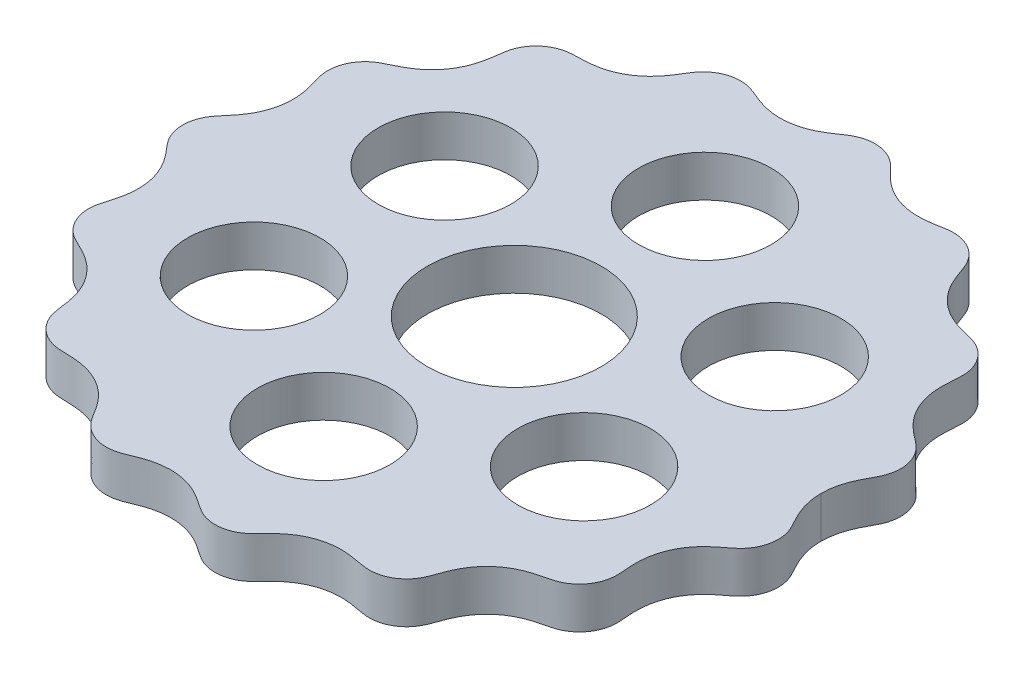
SolidWorks part; units mm, degrees
ref_plane "Front Plane" through (0, 0, 0) normal (0, 0, 1) x (1, 0, 0)
ref_plane "Top Plane" through (0, 0, 0) normal (0, 1, 0) x (1, 0, 0)
ref_plane "Right Plane" through (0, 0, 0) normal (1, 0, 0) x (0, 0, -1)
sketch "Sketch1" plane through (0, 0, 0) normal (0, 1, 0) x (1, 0, 0)
  circle A0 centre (0, 0) radius 10.5
  circle A1 centre (0, 0) radius 23 construction
  circle A2 centre (0, 23) radius 8
  circle A3 centre (19.9186, 11.5) radius 8
  circle A4 centre (19.9186, -11.5) radius 8
  circle A5 centre (0, -23) radius 8
  circle A6 centre (-19.9186, -11.5) radius 8
  circle A7 centre (-19.9186, 11.5) radius 8
  spline S0 degree 4 poles (38.6756, 9.5405) (38.7869, 9.3354) (38.9807, 8.9098) (39.18, 8.2438) (39.2638, 7.3275) (39.17, 6.4698) (38.9321, 5.7015) (38.5995, 5.0253) (38.2553, 4.4109) (37.9563, 3.8443) (37.7129, 3.322) (37.522, 2.8468) (37.3939, 2.4766) (37.2981, 2.1548) (37.2278, 1.884) (37.1776, 1.6659) (37.1334, 1.4465) (37.0953, 1.226) (37.0635, 1.0045) (37.0411, 0.8091) (37.0259, 0.6435) (37.0159, 0.5055) (37.0095, 0.392) (37.0035, 0.2438) (36.9999, 0.079) (36.9994, -0.0361) (37.0025, -0.21) (37.0079, -0.366) (37.0181, -0.5474) (37.0358, -0.7626) (37.0623, -1.0007) (37.0996, -1.2541) (37.1417, -1.4901) (37.1867, -1.7077) (37.276, -2.0862) (37.4326, -2.6197) (37.6503, -3.1917) (37.9334, -3.7956) (38.206, -4.3157) (38.4505, -4.7606) (38.7069, -5.2352) (38.9418, -5.7567) (39.1379, -6.3788) (39.248, -7.1039) (39.2286, -7.94) (39.0193, -8.8558) (38.5776, -9.8235) (37.821, -10.7544) (36.8481, -11.435) (35.9255, -12.1707) (35.1552, -12.9314) (34.5438, -13.6951) (33.8952, -14.742) (33.4284, -15.8904) (33.1613, -17.1041) (33.0908, -18.2767) (33.1179, -19.1348) (33.1846, -19.9227) (33.2426, -20.6446) (33.2196, -21.4379) (33.0363, -22.2817) (32.6622, -23.1285) (32.0787, -23.9264) (31.2705, -24.6475) (30.2129, -25.1958) (29.0562, -25.4259) (27.9212, -25.7148) (26.9129, -26.088) (26.0467, -26.5265) (25.2315, -27.0702) (24.4863, -27.7162) (23.8232, -28.4568) (23.2548, -29.2804) (22.819, -30.1054) (22.4892, -30.9045) (22.2262, -31.656) (21.9863, -32.3444) (21.6457, -33.0672) (21.1369, -33.7721) (20.4446, -34.4052) (19.5735, -34.9081) (18.6791, -35.1912) (17.8142, -35.2793) (17.018, -35.2129) (16.3018, -35.0765) (15.5195, -34.9284) (14.6625, -34.8147) (13.4804, -34.7697) (12.2411, -34.9196) (11.052, -35.2755) (9.9494, -35.8202) (9.1364, -36.3513) (8.3091, -37.0378) (7.4914, -37.8764) (6.7137, -38.763) (5.7101, -39.4048) (4.6815, -39.7442) (3.6987, -39.8506) (2.7784, -39.7512) (1.9559, -39.488) (1.2575, -39.1113) (0.6613, -38.7001) (0.0122, -38.2484) (-0.7173, -37.7958) (-1.768, -37.2706) (-2.9527, -36.8951) (-4.1807, -36.7251) (-5.4116, -36.7634) (-6.3787, -36.9109) (-7.4226, -37.1978) (-8.5211, -37.6287) (-9.5969, -38.1313) (-10.7814, -38.3206) (-11.8653, -38.2177) (-12.81, -37.9179) (-13.7654, -37.3701) (-14.6397, -36.51) (-15.225, -35.4471) (-15.8752, -34.4321) (-16.7227, -33.382) (-17.6452, -32.5494) (-18.6953, -31.8812) (-19.8393, -31.4031) (-20.7931, -31.1347) (-21.8817, -30.9645) (-23.0854, -30.9087) (-24.2988, -30.9334) (-25.4807, -30.6062) (-26.4329, -30.0527) (-27.1648, -29.3844) (-27.7959, -28.4973) (-28.2242, -27.3768) (-28.3269, -26.1938) (-28.503, -25.027) (-28.7764, -23.9796) (-29.1322, -23.0683) (-29.7145, -21.9831) (-30.4757, -21.0047) (-31.3933, -20.1664) (-32.3735, -19.5191) (-33.1302, -19.1136) (-33.8459, -18.7774) (-34.5001, -18.4667) (-35.1756, -18.0501) (-35.8147, -17.4694) (-36.361, -16.7221) (-36.7603, -15.8178) (-36.9806, -14.7573) (-36.9266, -13.5673) (-36.5476, -12.4504) (-36.2302, -11.323) (-36.0493, -10.2632) (-35.996, -9.2938) (-36.0592, -8.316) (-36.2461, -7.3476) (-36.5559, -6.4031) (-36.985, -5.499) (-37.4816, -4.7092) (-38.0086, -4.024) (-38.5281, -3.4205) (-39.0041, -2.8683) (-39.353, -2.3666) (-39.5782, -1.9309) (-39.7176, -1.5888) (-39.7983, -1.3525) (-39.8659, -1.1123) (-39.9132, -0.899) (-39.9453, -0.714) (-39.9664, -0.5608) (-39.98, -0.4381) (-39.9901, -0.3108) (-39.9969, -0.1759) (-40.0009, -0.0264) (-39.9998, 0.101) (-39.9919, 0.3019) (-39.9779, 0.461) (-39.962, 0.5936) (-39.9468, 0.7) (-39.9245, 0.8336) (-39.8928, 0.9931) (-39.8356, 1.2296) (-39.7321, 1.5628) (-39.5698, 1.9581) (-39.3263, 2.4015) (-39.0212, 2.8342) (-38.6301, 3.3062) (-38.1713, 3.8306) (-37.748, 4.3543) (-37.3751, 4.8861) (-37.0367, 5.4401) (-36.6355, 6.2077) (-36.2169, 7.3272) (-36.0304, 8.4018) (-36.0089, 9.2689) (-36.0283, 9.7011) knots 0 0 0 0 0 0.006139 0.012278 0.018165 0.024053 0.028687 0.033322 0.037957 0.042591 0.045535 0.048479 0.051424 0.052896 0.054368 0.05584 0.057312 0.058784 0.060256 0.061728 0.062464 0.0632 0.063936 0.064672 0.066144 0.067103 0.068061 0.06902 0.069978 0.071895 0.073812 0.075274 0.076735 0.078197 0.079659 0.085505 0.091352 0.094275 0.097198 0.100954 0.104711 0.108467 0.112223 0.11807 0.123916 0.130339 0.136761 0.145879 0.154997 0.161421 0.167846 0.17427 0.180694 0.193737 0.200258 0.206779 0.211542 0.216304 0.221067 0.225829 0.232349 0.238869 0.245245 0.251622 0.260677 0.269731 0.27611 0.282488 0.288866 0.295244 0.301811 0.308378 0.314945 0.321512 0.326307 0.331102 0.335897 0.340691 0.347256 0.353821 0.360386 0.366951 0.371745 0.37654 0.381335 0.38613 0.392697 0.399264 0.412398 0.418776 0.425154 0.431532 0.437911 0.446965 0.45602 0.462396 0.468773 0.475293 0.481813 0.486575 0.491338 0.4961 0.500863 0.507384 0.513905 0.526948 0.533372 0.539796 0.54622 0.552645 0.561763 0.570881 0.577303 0.583726 0.59023 0.596734 0.606103 0.615471 0.621978 0.628484 0.641498 0.648004 0.654511 0.661018 0.667524 0.676893 0.686261 0.692765 0.699269 0.705692 0.712114 0.721232 0.730351 0.736775 0.743199 0.749623 0.756047 0.76909 0.775611 0.782133 0.786895 0.791658 0.79642 0.801182 0.807702 0.814222 0.820599 0.826976 0.83603 0.845085 0.851463 0.857841 0.864219 0.870597 0.877164 0.883732 0.890299 0.896866 0.90166 0.906455 0.91125 0.916045 0.917686 0.919327 0.920968 0.922609 0.924251 0.925071 0.925892 0.926712 0.927533 0.928354 0.929174 0.930597 0.93202 0.932732 0.933444 0.934155 0.934867 0.93629 0.937713 0.940559 0.944036 0.947513 0.950991 0.954468 0.960159 0.965851 0.968697 0.971542 0.977234 0.988617 1 1 1 1 1 construction
  spline S1 degree 4 poles (37, 0) (37, -0.0314) (37.0005, -0.095) (37.0025, -0.21) (37.0079, -0.366) (37.0181, -0.5474) (37.0358, -0.7626) (37.0623, -1.0007) (37.0996, -1.2541) (37.1417, -1.4901) (37.1867, -1.7077) (37.276, -2.0862) (37.4326, -2.6197) (37.6503, -3.1917) (37.9334, -3.7956) (38.206, -4.3157) (38.4505, -4.7606) (38.7069, -5.2352) (38.9418, -5.7567) (39.1379, -6.3788) (39.248, -7.1039) (39.2286, -7.94) (39.0193, -8.8558) (38.5776, -9.8235) (37.821, -10.7544) (36.8481, -11.435) (35.9255, -12.1707) (35.1552, -12.9314) (34.5438, -13.6951) (33.8952, -14.742) (33.4284, -15.8904) (33.1613, -17.1041) (33.0908, -18.2767) (33.1179, -19.1348) (33.1846, -19.9227) (33.2426, -20.6446) (33.2196, -21.4379) (33.0363, -22.2817) (32.6622, -23.1285) (32.0787, -23.9264) (31.2705, -24.6475) (30.2129, -25.1958) (29.0562, -25.4259) (27.9212, -25.7148) (26.9129, -26.088) (26.0467, -26.5265) (25.2315, -27.0702) (24.4863, -27.7162) (23.8232, -28.4568) (23.2548, -29.2804) (22.819, -30.1054) (22.4892, -30.9045) (22.2262, -31.656) (21.9863, -32.3444) (21.6457, -33.0672) (21.1369, -33.7721) (20.4446, -34.4052) (19.5735, -34.9081) (18.6791, -35.1912) (17.8142, -35.2793) (17.018, -35.2129) (16.3018, -35.0765) (15.5195, -34.9284) (14.6625, -34.8147) (13.4804, -34.7697) (12.2411, -34.9196) (11.052, -35.2755) (9.9494, -35.8202) (9.1364, -36.3513) (8.3091, -37.0378) (7.4914, -37.8764) (6.7137, -38.763) (5.7101, -39.4048) (4.6815, -39.7442) (3.6987, -39.8506) (2.7784, -39.7512) (1.9559, -39.488) (1.2575, -39.1113) (0.6613, -38.7001) (0.0122, -38.2484) (-0.7173, -37.7958) (-1.768, -37.2706) (-2.9527, -36.8951) (-4.1807, -36.7251) (-5.4116, -36.7634) (-6.3787, -36.9109) (-7.4226, -37.1978) (-8.5211, -37.6287) (-9.5969, -38.1313) (-10.7814, -38.3206) (-11.8653, -38.2177) (-12.81, -37.9179) (-13.7654, -37.3701) (-14.6397, -36.51) (-15.225, -35.4471) (-15.8752, -34.4321) (-16.7227, -33.382) (-17.6452, -32.5494) (-18.6953, -31.8812) (-19.8393, -31.4031) (-20.7931, -31.1347) (-21.8817, -30.9645) (-23.0854, -30.9087) (-24.2988, -30.9334) (-25.4807, -30.6062) (-26.4329, -30.0527) (-27.1648, -29.3844) (-27.7959, -28.4973) (-28.2242, -27.3768) (-28.3269, -26.1938) (-28.503, -25.027) (-28.7764, -23.9796) (-29.1322, -23.0683) (-29.7145, -21.9831) (-30.4757, -21.0047) (-31.3933, -20.1664) (-32.3735, -19.5191) (-33.1302, -19.1136) (-33.8459, -18.7774) (-34.5001, -18.4667) (-35.1756, -18.0501) (-35.8147, -17.4694) (-36.361, -16.7221) (-36.7603, -15.8178) (-36.9806, -14.7573) (-36.9266, -13.5673) (-36.5476, -12.4504) (-36.2302, -11.323) (-36.0493, -10.2632) (-35.996, -9.2938) (-36.0592, -8.316) (-36.2461, -7.3476) (-36.5559, -6.4031) (-36.985, -5.499) (-37.4816, -4.7092) (-38.0086, -4.024) (-38.5281, -3.4205) (-39.0041, -2.8683) (-39.353, -2.3666) (-39.5782, -1.9309) (-39.7176, -1.5888) (-39.7983, -1.3525) (-39.8659, -1.1123) (-39.9132, -0.899) (-39.9453, -0.714) (-39.9664, -0.5608) (-39.98, -0.4381) (-39.9901, -0.3108) (-39.9969, -0.1759) (-39.9994, -0.0812) (-40, -0.0269) (-40, 0) knots 0.066144 0.066144 0.066144 0.066144 0.066144 0.067103 0.068061 0.06902 0.069978 0.071895 0.073812 0.075274 0.076735 0.078197 0.079659 0.085505 0.091352 0.094275 0.097198 0.100954 0.104711 0.108467 0.112223 0.11807 0.123916 0.130339 0.136761 0.145879 0.154997 0.161421 0.167846 0.17427 0.180694 0.193737 0.200258 0.206779 0.211542 0.216304 0.221067 0.225829 0.232349 0.238869 0.245245 0.251622 0.260677 0.269731 0.27611 0.282488 0.288866 0.295244 0.301811 0.308378 0.314945 0.321512 0.326307 0.331102 0.335897 0.340691 0.347256 0.353821 0.360386 0.366951 0.371745 0.37654 0.381335 0.38613 0.392697 0.399264 0.412398 0.418776 0.425154 0.431532 0.437911 0.446965 0.45602 0.462396 0.468773 0.475293 0.481813 0.486575 0.491338 0.4961 0.500863 0.507384 0.513905 0.526948 0.533372 0.539796 0.54622 0.552645 0.561763 0.570881 0.577303 0.583726 0.59023 0.596734 0.606103 0.615471 0.621978 0.628484 0.641498 0.648004 0.654511 0.661018 0.667524 0.676893 0.686261 0.692765 0.699269 0.705692 0.712114 0.721232 0.730351 0.736775 0.743199 0.749623 0.756047 0.76909 0.775611 0.782133 0.786895 0.791658 0.79642 0.801182 0.807702 0.814222 0.820599 0.826976 0.83603 0.845085 0.851463 0.857841 0.864219 0.870597 0.877164 0.883732 0.890299 0.896866 0.90166 0.906455 0.91125 0.916045 0.917686 0.919327 0.920968 0.922609 0.924251 0.925071 0.925892 0.926712 0.927533 0.928354 0.929174 0.929174 0.929174 0.929174 0.929174
  spline S2 degree 4 poles (-36.0283, -9.7011) (-36.0089, -9.2689) (-36.025, -8.6185) (-36.1423, -7.7571) (-36.4452, -6.7165) (-36.7773, -5.9157) (-37.1923, -5.1548) (-37.6189, -4.528) (-38.0202, -4.0177) (-38.3849, -3.5864) (-38.6992, -3.2229) (-38.979, -2.8851) (-39.2119, -2.5638) (-39.3869, -2.2834) (-39.514, -2.0514) (-39.6452, -1.7744) (-39.7518, -1.4995) (-39.8356, -1.2297) (-39.8991, -0.9667) (-39.9398, -0.7534) (-39.9703, -0.5412) (-39.9907, -0.329) (-39.9998, -0.1024) (-40.0009, 0.0274) (-39.9969, 0.174) (-39.9901, 0.3085) (-39.98, 0.4378) (-39.9664, 0.5616) (-39.9495, 0.6838) (-39.9292, 0.8064) (-39.9056, 0.9291) (-39.8785, 1.0511) (-39.8405, 1.2024) (-39.7882, 1.382) (-39.7175, 1.5887) (-39.6127, 1.8466) (-39.4787, 2.1231) (-39.3107, 2.4141) (-39.1049, 2.7153) (-38.8813, 3.0032) (-38.6471, 3.2825) (-38.3498, 3.6277) (-37.9529, 4.0962) (-37.4817, 4.7093) (-36.9849, 5.4989) (-36.556, 6.4033) (-36.1702, 7.5783) (-35.9868, 8.7988) (-36.0091, 10.0244) (-36.2006, 11.152) (-36.4085, 11.955) (-36.6307, 12.6803) (-36.8216, 13.3417) (-36.9923, 14.3318) (-36.9049, 15.4222) (-36.5044, 16.5243) (-35.815, 17.4697) (-35.1754, 18.05) (-34.5001, 18.4666) (-33.846, 18.7777) (-32.9056, 19.2181) (-31.7252, 19.8872) (-30.4396, 20.9666) (-29.2852, 22.5861) (-28.6866, 24.1372) (-28.4341, 25.439) (-28.3116, 26.4395) (-28.2186, 27.1266) (-28.0361, 27.8709) (-27.6947, 28.6385) (-27.1647, 29.385) (-26.4334, 30.0526) (-25.6346, 30.5161) (-24.8231, 30.7888) (-24.0469, 30.8992) (-23.3347, 30.9203) (-22.3064, 30.9378) (-20.9635, 31.0586) (-19.3449, 31.507) (-17.6134, 32.5067) (-16.4158, 33.6842) (-15.6397, 34.7868) (-15.1104, 35.6686) (-14.7361, 36.2748) (-14.2524, 36.8918) (-13.6104, 37.4583) (-12.8096, 37.9183) (-11.8658, 38.2178) (-10.9543, 38.3035) (-10.1188, 38.2154) (-9.383, 38.0014) (-8.7414, 37.7383) (-7.8138, 37.3442) (-6.5601, 36.912) (-4.9175, 36.6548) (-2.9379, 36.8448) (-1.3603, 37.4184) (-0.1906, 38.1061) (0.661, 38.7003) (1.2575, 39.1113) (1.9559, 39.4878) (2.7783, 39.7515) (3.9418, 39.8759) (5.0965, 39.6717) (6.0845, 39.2022) (6.8565, 38.5593) (7.3339, 38.0633) (7.8509, 37.5082) (8.4424, 36.9267) (9.3231, 36.1969) (10.5884, 35.4356) (11.9992, 34.9487) (13.4803, 34.7698) (14.6625, 34.8147) (15.5194, 34.9284) (16.3018, 35.0765) (17.0179, 35.2129) (17.8142, 35.2793) (18.6791, 35.1911) (19.5735, 34.9082) (20.4445, 34.4052) (21.137, 33.7722) (21.5918, 33.1415) (21.8696, 32.5926) (22.0759, 32.0862) (22.2266, 31.6561) (22.3766, 31.2261) (22.5937, 30.6514) (22.8615, 30.0249) (23.2551, 29.2802) (23.8228, 28.4571) (24.6491, 27.5346) (25.8025, 26.6152) (27.2181, 25.9053) (28.8176, 25.4727) (30.4528, 25.1488) (31.6988, 24.3833) (32.5609, 23.3518) (33.0376, 22.2818) (33.2189, 21.4379) (33.243, 20.6446) (33.1848, 19.9227) (33.0963, 18.888) (33.0853, 17.5312) (33.3775, 15.8781) (34.2027, 14.0687) (35.2468, 12.7747) (36.2479, 11.9052) (37.0531, 11.2989) (37.6016, 10.8748) (38.155, 10.3445) (38.649, 9.665) (39.0305, 8.8328) (39.243, 7.8658) (39.2451, 6.9422) (39.0753, 6.1031) (38.7832, 5.3754) (38.4446, 4.7486) (38.1266, 4.173) (37.8549, 3.634) (37.633, 3.1317) (37.4786, 2.7272) (37.3626, 2.3747) (37.2774, 2.0775) (37.2164, 1.8379) (37.1626, 1.5964) (37.1163, 1.3536) (37.0774, 1.1094) (37.0502, 0.8937) (37.0316, 0.7109) (37.0194, 0.5584) (37.0116, 0.4331) (37.0042, 0.2696) (36.9994, 0.0658) (36.9993, -0.087) (37.0071, -0.3742) (37.0226, -0.616) (37.0458, -0.8587) (37.0767, -1.1038) (37.1247, -1.4076) (37.1852, -1.7092) (37.2578, -2.0082) (37.3591, -2.3632) (37.4739, -2.7141) (37.627, -3.1167) (37.8469, -3.6171) (38.1165, -4.154) (38.4326, -4.7273) (38.7709, -5.3508) (39.0661, -6.0733) (39.2414, -6.9072) (39.2472, -7.9128) (39.0566, -8.7198) (38.8323, -9.2517) (38.6756, -9.5405) knots 0 0 0 0 0 0.011383 0.017074 0.022766 0.028458 0.034149 0.039841 0.042687 0.045532 0.049009 0.052487 0.054225 0.055964 0.057702 0.059441 0.062287 0.06371 0.065133 0.066556 0.06798 0.069403 0.070826 0.071646 0.072467 0.073288 0.074108 0.074929 0.075749 0.07657 0.077391 0.078211 0.079032 0.080673 0.082314 0.083955 0.086353 0.08875 0.091148 0.093545 0.095942 0.09834 0.103134 0.109701 0.116269 0.122836 0.129403 0.142159 0.148537 0.154915 0.159443 0.16397 0.168497 0.173024 0.185778 0.192298 0.198818 0.20358 0.208342 0.213105 0.217867 0.23091 0.243953 0.256801 0.269649 0.274209 0.278768 0.283327 0.287886 0.294308 0.300731 0.307235 0.313739 0.318423 0.323107 0.327792 0.332476 0.345489 0.358502 0.371516 0.384529 0.389213 0.393897 0.398582 0.403266 0.40977 0.416274 0.422697 0.429119 0.433678 0.438237 0.442796 0.447355 0.460204 0.473052 0.486095 0.499137 0.5039 0.508662 0.513425 0.518187 0.524707 0.531227 0.54398 0.548508 0.553035 0.557562 0.56209 0.568468 0.574846 0.587602 0.600736 0.607303 0.613871 0.618665 0.62346 0.628255 0.633049 0.639614 0.646179 0.652744 0.659309 0.664104 0.666501 0.668898 0.673693 0.67609 0.678488 0.685055 0.691622 0.698189 0.704756 0.717512 0.730269 0.739323 0.748378 0.761131 0.767651 0.774171 0.778933 0.783696 0.788458 0.793221 0.806263 0.819306 0.832154 0.845003 0.849562 0.854121 0.85868 0.863239 0.869662 0.876084 0.882588 0.889092 0.893777 0.898461 0.903145 0.907829 0.911083 0.914336 0.917589 0.919216 0.920842 0.922469 0.924096 0.925722 0.927349 0.928976 0.929789 0.930602 0.931416 0.932229 0.933856 0.935474 0.937093 0.938711 0.94033 0.941948 0.943567 0.946804 0.948422 0.950041 0.953278 0.956515 0.959752 0.964416 0.96908 0.973744 0.978408 0.984882 0.991355 1 1 1 1 1 construction
  spline S3 degree 4 poles (-40, 0) (-40, 0.0269) (-39.9994, 0.0811) (-39.9969, 0.174) (-39.9901, 0.3085) (-39.98, 0.4378) (-39.9664, 0.5616) (-39.9495, 0.6838) (-39.9292, 0.8064) (-39.9056, 0.9291) (-39.8785, 1.0511) (-39.8405, 1.2024) (-39.7882, 1.382) (-39.7175, 1.5887) (-39.6127, 1.8466) (-39.4787, 2.1231) (-39.3107, 2.4141) (-39.1049, 2.7153) (-38.8813, 3.0032) (-38.6471, 3.2825) (-38.3498, 3.6277) (-37.9529, 4.0962) (-37.4817, 4.7093) (-36.9849, 5.4989) (-36.556, 6.4033) (-36.1702, 7.5783) (-35.9868, 8.7988) (-36.0091, 10.0244) (-36.2006, 11.152) (-36.4085, 11.955) (-36.6307, 12.6803) (-36.8216, 13.3417) (-36.9923, 14.3318) (-36.9049, 15.4222) (-36.5044, 16.5243) (-35.815, 17.4697) (-35.1754, 18.05) (-34.5001, 18.4666) (-33.846, 18.7777) (-32.9056, 19.2181) (-31.7252, 19.8872) (-30.4396, 20.9666) (-29.2852, 22.5861) (-28.6866, 24.1372) (-28.4341, 25.439) (-28.3116, 26.4395) (-28.2186, 27.1266) (-28.0361, 27.8709) (-27.6947, 28.6385) (-27.1647, 29.385) (-26.4334, 30.0526) (-25.6346, 30.5161) (-24.8231, 30.7888) (-24.0469, 30.8992) (-23.3347, 30.9203) (-22.3064, 30.9378) (-20.9635, 31.0586) (-19.3449, 31.507) (-17.6134, 32.5067) (-16.4158, 33.6842) (-15.6397, 34.7868) (-15.1104, 35.6686) (-14.7361, 36.2748) (-14.2524, 36.8918) (-13.6104, 37.4583) (-12.8096, 37.9183) (-11.8658, 38.2178) (-10.9543, 38.3035) (-10.1188, 38.2154) (-9.383, 38.0014) (-8.7414, 37.7383) (-7.8138, 37.3442) (-6.5601, 36.912) (-4.9175, 36.6548) (-2.9379, 36.8448) (-1.3603, 37.4184) (-0.1906, 38.1061) (0.661, 38.7003) (1.2575, 39.1113) (1.9559, 39.4878) (2.7783, 39.7515) (3.9418, 39.8759) (5.0965, 39.6717) (6.0845, 39.2022) (6.8565, 38.5593) (7.3339, 38.0633) (7.8509, 37.5082) (8.4424, 36.9267) (9.3231, 36.1969) (10.5884, 35.4356) (11.9992, 34.9487) (13.4803, 34.7698) (14.6625, 34.8147) (15.5194, 34.9284) (16.3018, 35.0765) (17.0179, 35.2129) (17.8142, 35.2793) (18.6791, 35.1911) (19.5735, 34.9082) (20.4445, 34.4052) (21.137, 33.7722) (21.5918, 33.1415) (21.8696, 32.5926) (22.0759, 32.0862) (22.2266, 31.6561) (22.3766, 31.2261) (22.5937, 30.6514) (22.8615, 30.0249) (23.2551, 29.2802) (23.8228, 28.4571) (24.6491, 27.5346) (25.8025, 26.6152) (27.2181, 25.9053) (28.8176, 25.4727) (30.4528, 25.1488) (31.6988, 24.3833) (32.5609, 23.3518) (33.0376, 22.2818) (33.2189, 21.4379) (33.243, 20.6446) (33.1848, 19.9227) (33.0963, 18.888) (33.0853, 17.5312) (33.3775, 15.8781) (34.2027, 14.0687) (35.2468, 12.7747) (36.2479, 11.9052) (37.0531, 11.2989) (37.6016, 10.8748) (38.155, 10.3445) (38.649, 9.665) (39.0305, 8.8328) (39.243, 7.8658) (39.2451, 6.9422) (39.0753, 6.1031) (38.7832, 5.3754) (38.4446, 4.7486) (38.1266, 4.173) (37.8549, 3.634) (37.633, 3.1317) (37.4786, 2.7272) (37.3626, 2.3747) (37.2774, 2.0775) (37.2164, 1.8379) (37.1626, 1.5964) (37.1163, 1.3536) (37.0774, 1.1094) (37.0502, 0.8937) (37.0316, 0.7109) (37.0194, 0.5584) (37.0116, 0.4331) (37.0042, 0.2696) (37.001, 0.1335) (37, 0.0534) (37, 0) knots 0.070826 0.070826 0.070826 0.070826 0.070826 0.071646 0.072467 0.073288 0.074108 0.074929 0.075749 0.07657 0.077391 0.078211 0.079032 0.080673 0.082314 0.083955 0.086353 0.08875 0.091148 0.093545 0.095942 0.09834 0.103134 0.109701 0.116269 0.122836 0.129403 0.142159 0.148537 0.154915 0.159443 0.16397 0.168497 0.173024 0.185778 0.192298 0.198818 0.20358 0.208342 0.213105 0.217867 0.23091 0.243953 0.256801 0.269649 0.274209 0.278768 0.283327 0.287886 0.294308 0.300731 0.307235 0.313739 0.318423 0.323107 0.327792 0.332476 0.345489 0.358502 0.371516 0.384529 0.389213 0.393897 0.398582 0.403266 0.40977 0.416274 0.422697 0.429119 0.433678 0.438237 0.442796 0.447355 0.460204 0.473052 0.486095 0.499137 0.5039 0.508662 0.513425 0.518187 0.524707 0.531227 0.54398 0.548508 0.553035 0.557562 0.56209 0.568468 0.574846 0.587602 0.600736 0.607303 0.613871 0.618665 0.62346 0.628255 0.633049 0.639614 0.646179 0.652744 0.659309 0.664104 0.666501 0.668898 0.673693 0.67609 0.678488 0.685055 0.691622 0.698189 0.704756 0.717512 0.730269 0.739323 0.748378 0.761131 0.767651 0.774171 0.778933 0.783696 0.788458 0.793221 0.806263 0.819306 0.832154 0.845003 0.849562 0.854121 0.85868 0.863239 0.869662 0.876084 0.882588 0.889092 0.893777 0.898461 0.903145 0.907829 0.911083 0.914336 0.917589 0.919216 0.920842 0.922469 0.924096 0.925722 0.927349 0.928976 0.929789 0.930602 0.931416 0.932229 0.933856 0.933856 0.933856 0.933856 0.933856
  point P24 (0, 0)
  dimension "D1" = 21
  dimension "D2" = 16
  dimension "D4" = 46
  dimension "D3" = 6
extrude "Boss-Extrude1" add sketch "Sketch1" along normal blind 5
